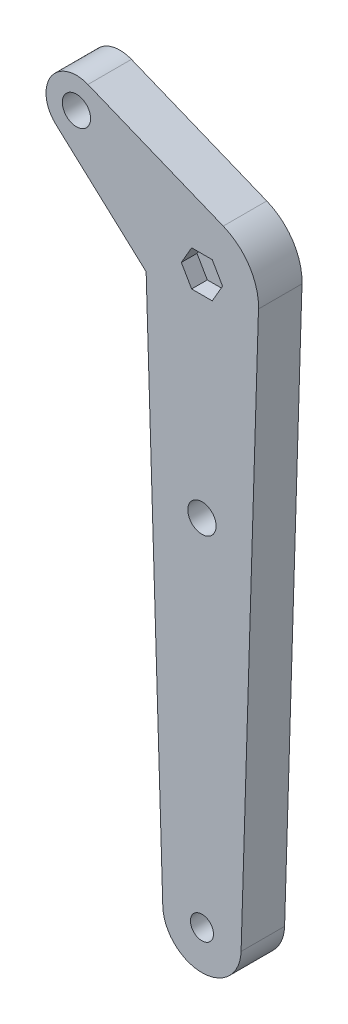
SolidWorks part; units mm, degrees
ref_plane "Front Plane" through (0, 0, 0) normal (0, 0, 1) x (1, 0, 0)
ref_plane "Top Plane" through (0, 0, 0) normal (0, 1, 0) x (1, 0, 0)
ref_plane "Right Plane" through (0, 0, 0) normal (1, 0, 0) x (0, 0, -1)
ref_plane "Plane1" through (0, 0, 348) normal (0, 0, 1) x (1, 0, 0)
sketch "Sketch1" plane through (0, 0, 348) normal (0, 0, 1) x (1, 0, 0)
  line L0 (287.0062, 169.6) -> (291.0043, 39.7231)
  line L1 (308.9957, 39.7231) -> (312.9938, 169.6)
  arc A0 (291.0043, 39.7231) -> (308.9957, 39.7231) centre (300, 40) ccw
  arc A1 (312.9938, 169.6) -> (287.0062, 169.6) centre (300, 170) ccw
  circle A2 centre (300, 170) radius 2.6
  circle A3 centre (300, 40) radius 2.65
extrude "Boss-Extrude1" add sketch "Sketch1" along normal blind 10
sketch "Sketch2" plane through (0, 0, 348) normal (0, 0, 1) x (1, 0, 0)
  line L0 (304.8942, 182.0436) -> (273.7972, 194.6805)
  line L1 (266.4431, 183.025) -> (291.2367, 160.3977)
  arc A0 (273.7972, 194.6805) -> (266.4431, 183.025) centre (271.1619, 188.1955) ccw
  arc A1 (291.2367, 160.3977) -> (304.8942, 182.0436) centre (300, 170) ccw
extrude "Boss-Extrude2" add sketch "Sketch2" along normal blind 10
ref_plane "Plane2" through (0, 0, 354.4) normal (0, 0, 1) x (1, 0, 0)
sketch "Sketch3" plane through (0, 0, 354.4) normal (0, 0, 1) x (1, 0, 0)
  line L0 (304.7343, 170) -> (302.3671, 174.1)
  line L1 (302.3671, 174.1) -> (297.6329, 174.1)
  line L2 (297.6329, 174.1) -> (295.2657, 170)
  line L3 (295.2657, 170) -> (297.6329, 165.9)
  line L4 (297.6329, 165.9) -> (302.3671, 165.9)
  line L5 (302.3671, 165.9) -> (304.7343, 170)
extrude "Cut-Extrude1" cut sketch "Sketch3" along normal blind 3.6
sketch "Sketch4" plane through (0, 0, 348) normal (0, 0, 1) x (1, 0, 0)
  circle A0 centre (300, 121.5) radius 3.25
  circle A1 centre (271.1619, 188.1955) radius 3.25
extrude "Cut-Extrude2" cut sketch "Sketch4" along normal blind 50
sketch "Sketch5" plane through (0, 0, 348) normal (0, 0, 1) x (1, 0, 0)
  circle A0 centre (300, 70) radius 2.05
extrude "Cut-Extrude3" cut sketch "Sketch5" along normal blind 6.7
ref_plane "Plane3" through (300, 0, 0) normal (1, 0, 0) x (0, 0, -1)
ref_plane "Plane4" through (0, 170, 0) normal (0, 1, 0) x (1, 0, 0)
ref_axis "KNEE_AXIS" through (300, 170, 358.5) along (0, 0, -1)
ref_plane "Plane5" through (0, 40, 0) normal (0, 1, 0) x (1, 0, 0)
ref_axis "ANKLE_AXIS" through (300, 40, 358.5) along (0, 0, -1)
